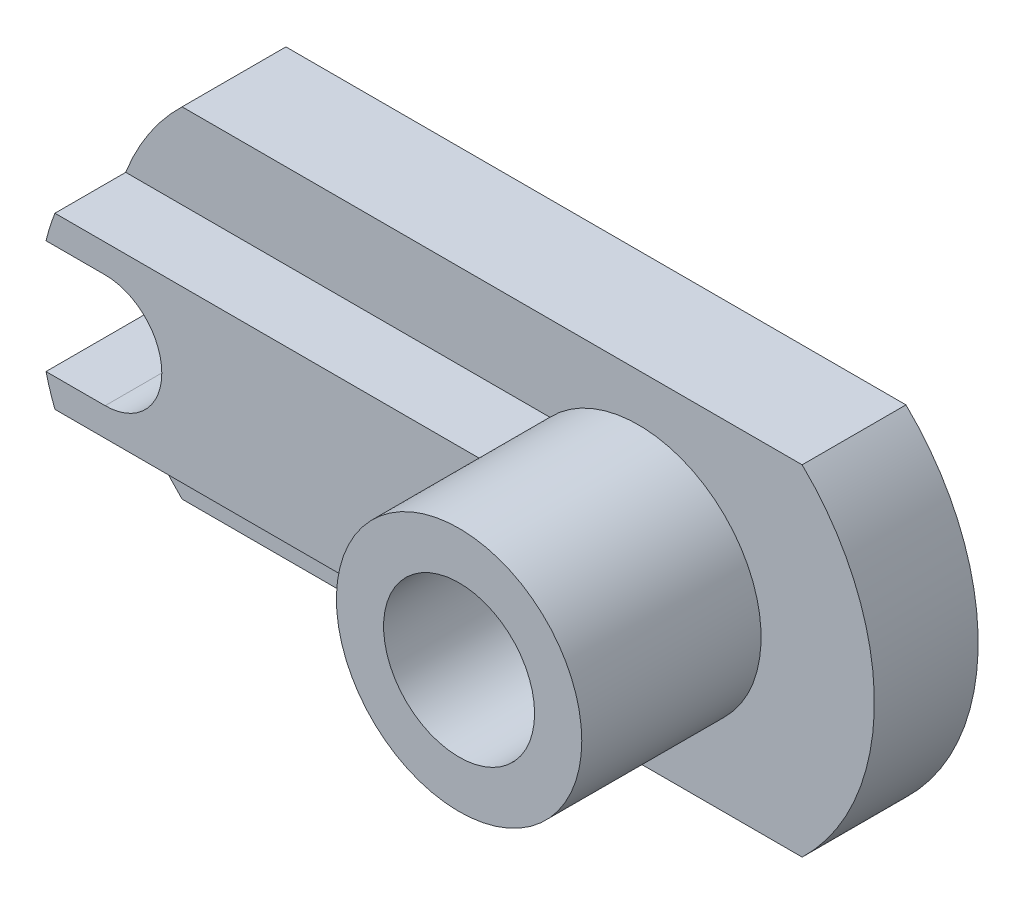
SolidWorks part; units mm, degrees
note: The reader was unsure of these and kept them because the rebuilt part matched: shared geometry of "Sketch2<3>".
ref_plane "Front Plane" through (0, 0, 0) normal (0, 0, 1) x (1, 0, 0)
ref_plane "Top Plane" through (0, 0, 0) normal (0, 1, 0) x (1, 0, 0)
ref_plane "Right Plane" through (0, 0, 0) normal (1, 0, 0) x (0, 0, -1)
sketch "Sketch1" plane through (0, 0, 0) normal (0, 0, 1) x (1, 0, 0)
  line L0 (-87.7987, 0) -> (75.8383, 0) construction
  line L1 (0, 34.2881) -> (0, -37.914) construction
  line L2 (-32.8494, -18) -> (32.8494, -18)
  line L3 (32.8494, 18) -> (-32.8494, 18)
  line L4 (-39.7693, -6) -> (-33.5, -6)
  line L5 (-39.7693, 6) -> (-33.5, 6)
  arc A1 (-32.8494, 18) -> (-39.7693, 6) centre (-15.5, 0) ccw
  arc A2 (32.8494, -18) -> (32.8494, 18) centre (15.5, 0) ccw
  arc A3 (-33.5, 6) -> (-33.5, -6) centre (-33.5, 0) cw
  arc A4 (-39.7693, -6) -> (-32.8494, -18) centre (-15.5, 0) ccw
  point P16 (-54.4162, 6)
  point P17 (52.6075, 18)
  point P18 (0, 0)
  point P19 (0, 0)
  point P20 (54.1423, -18)
  point P21 (-41.7195, -6)
  dimension "D1" = 6
  dimension "D2" = 25
  dimension "D3" = 25
  dimension "D5" = 49
  dimension "D4" = 36
  dimension "D6" = 31
extrude "Boss-Extrude1" add sketch "Sketch1" against normal blind 11
sketch "Sketch2" plane through (0, 0, 0) normal (0, 0, 1) x (1, 0, 0)
  line L0 (-52.4232, 0) -> (52.8403, 0) construction
  line L1 (0, 28.903) -> (0, -29.1121) construction
  line L2 (-38.8238, -9) -> (6.1192, -9)
  line L3 (-38.8238, 9) -> (6.1192, 9)
  circle A0 centre (15.5, 0) radius 13
  circle A1 centre (15.5, 0) radius 8
  arc A2 (-39.7693, -6) -> (-32.8494, -18) centre (-15.5, 0) ccw construction
  arc A3 (-32.8494, 18) -> (-39.7693, 6) centre (-15.5, 0) ccw construction
  dimension "D1" = 26
  dimension "D2" = 16
  dimension "D3" = 18
  dimension "D4" = 49
extrude "Boss-Extrude2" add sketch "Sketch2" along normal blind 7.5
extrude "Boss-Extrude3" add sketch "Sketch2<3>" along normal blind 19
sketch "Sketch2<3>" plane through (0, 0, 0) normal (0, 0, 1) x (1, 0, 0) same geometry as "Sketch2"
sketch "Sketch8" plane through (0, 0, 0) normal (0, 0, 1) x (1, 0, 0)
  circle A1 centre (15.5, 0) radius 8
  circle A2 centre (15.5, 0) radius 8
  dimension "D1" = 0
extrude "Cut-Extrude1" cut sketch "Sketch8" against normal blind 19
